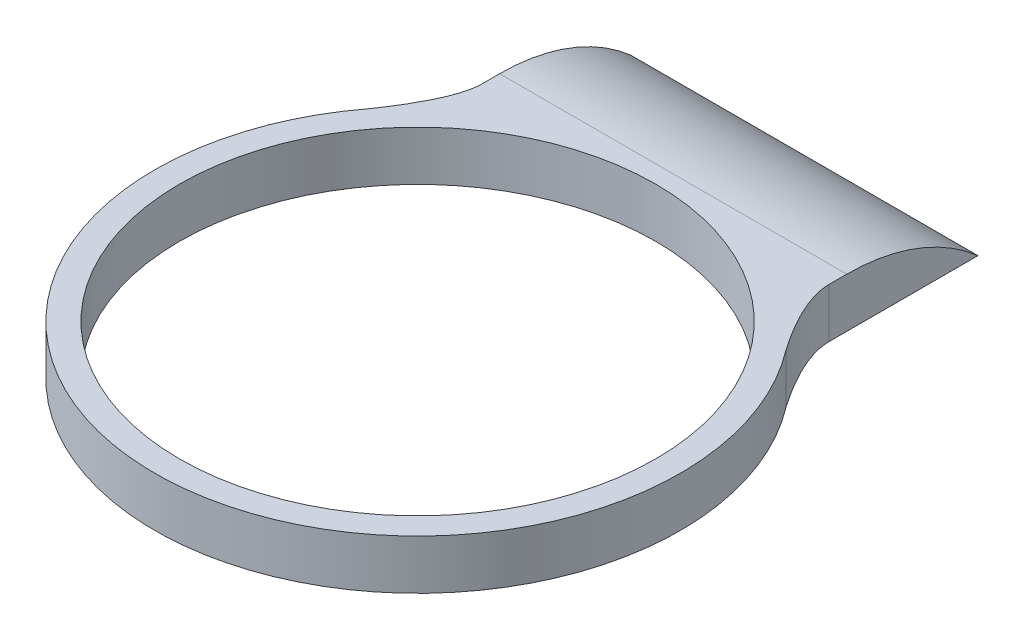
SolidWorks part; units mm, degrees
ref_plane "Front Plane" through (0, 0, 0) normal (0, 0, 1) x (1, 0, 0)
ref_plane "Top Plane" through (0, 0, 0) normal (0, 1, 0) x (1, 0, 0)
ref_plane "Right Plane" through (0, 0, 0) normal (1, 0, 0) x (0, 0, -1)
sketch "Sketch1" plane through (0, 0, 0) normal (0, 1, 0) x (1, 0, 0)
  line L0 (0, 53) -> (0, 0) construction
  line L1 (-35, 78) -> (35, 78)
  line L2 (-35, 78) -> (-35, 48)
  line L3 (-35, 48) -> (35, 48)
  line L4 (35, 78) -> (35, 48)
  circle A0 centre (0, 0) radius 48
  circle A1 centre (0, 0) radius 53
  spline S0 degree 2 poles (-35, 48) (-34.9936, 42.5163) (-42.0937, 32.2043) knots 0 0 0 1 1 1
  spline S1 degree 2 poles (35, 48) (34.9936, 42.5163) (42.0937, 32.2043) knots 0 0 0 1 1 1
  point P10 (0, 48)
  dimension "D1" = 96
  dimension "D3" = 30
  dimension "D4" = 70
  dimension "D2" = 5
extrude "Boss-Extrude1" add sketch "Sketch1" along normal blind 10 contours L3 A1 A0 | L3 S0 A1 | A1 L3 L4 L1 L2 | L0 A1 L3 | A1 L0 L3 | S1 L3 A1 region at (8.4827, 0, -50.0083) region at (0, 0, -64.0086) region at (-8.4827, 0, -50.0083) region at (11.2361, 0, -47.8536) region at (32.4099, 0, -44.1121) region at (-32.4099, 0, -44.1121)
fillet "Fillet1" radius 40 1 edges at (0, 10, -78)
